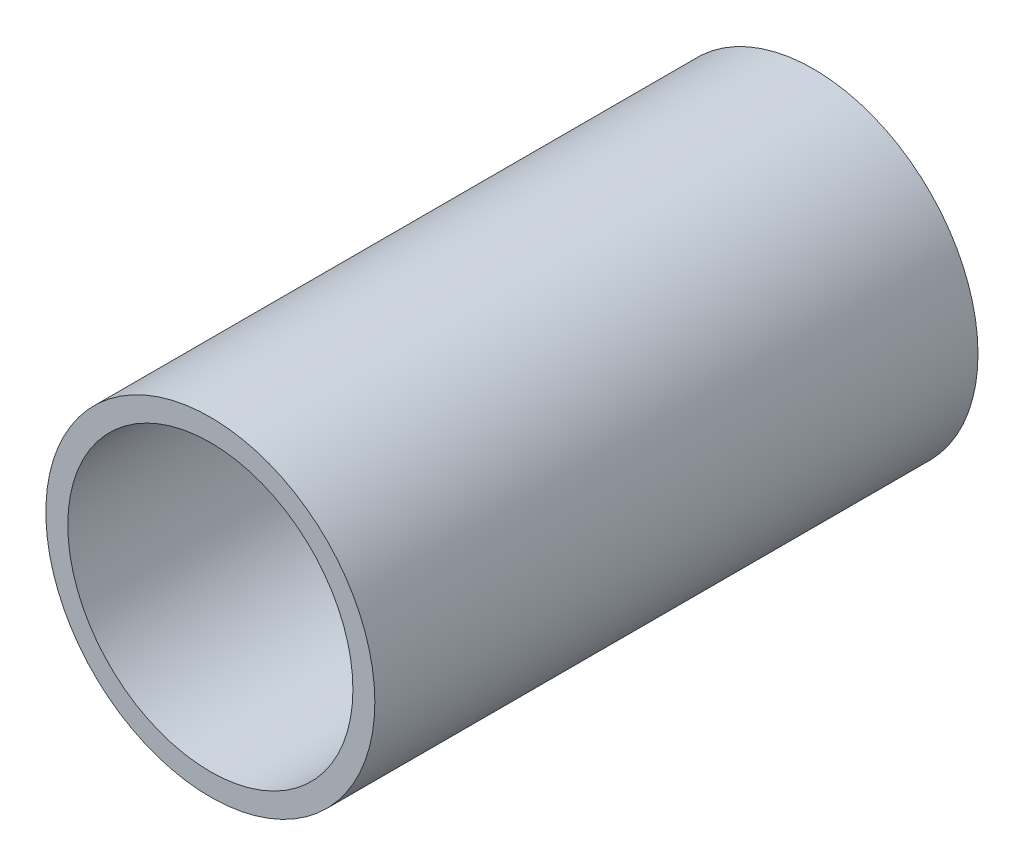
SolidWorks part; units mm, degrees
ref_plane "Front" through (0, 0, 0) normal (0, 0, 1) x (1, 0, 0)
ref_plane "Top" through (0, 0, 0) normal (0, 1, 0) x (1, 0, 0)
ref_plane "Right" through (0, 0, 0) normal (1, 0, 0) x (0, 0, -1)
sketch "Эскиз1" plane through (0, 0, 0) normal (0, 0, 1) x (1, 0, 0)
  circle A0 centre (0, 0) radius 52
  circle A1 centre (0, 0) radius 60
  dimension "D1" = 120
  dimension "D2" = 104
extrude "Бобышка-Вытянуть1" add sketch "Эскиз1" along normal blind 220
